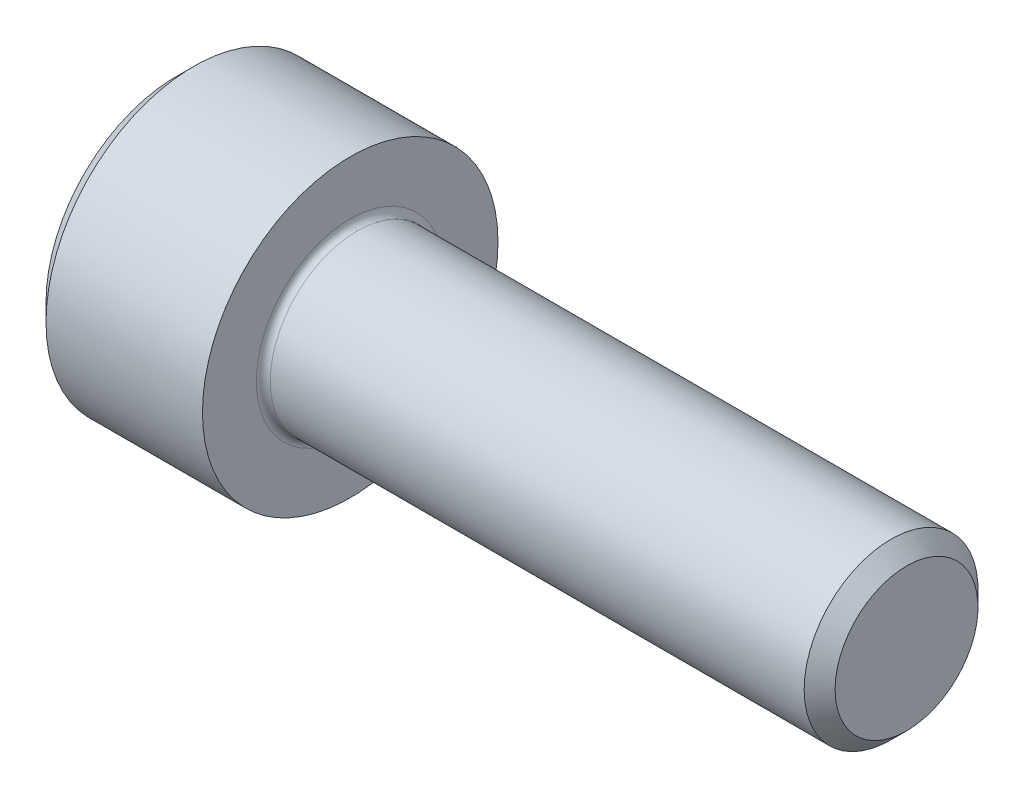
SolidWorks part; units mm, degrees
note: '?' marks a value the reader was unsure of.
revolve "Base-Revolve" add sketch "BodySke"
sketch "BodySke" plane through (0, 0, 0) normal (0, 0, 1) x (1, 0, 0)
  line L0 (0, 0) -> (0, 3.75)
  line L1 (0.5, 4.25) -> (5, 4.25)
  line L2 (5, 4.25) -> (5, 2.5)
  line L3 (5, 2.5) -> (20.555, 2.5)
  line L4 (21, 2.055) -> (21, 0)
  line L5 (21, 0) -> (0, 0)
  line L6 (-31.75, 0) -> (127, 0) construction
  line L7 (0, 3.75) -> (0.5, 4.25)
  line L8 (21, 2.055) -> (20.555, 2.5)
  line L9 (0, -3.75) -> (0.5, -4.25) construction
  line L10 (21, -2.055) -> (20.555, -2.5) construction
  line L11 (5.8, 9.525) -> (5.8, 3.175) construction
  line L12 (13, 9.525) -> (13, 3.175) construction
  line L13 (-29, 9.525) -> (-29, 3.175) construction
  dimension "Diameter" = 5
  dimension "Head_ht" = 5
  dimension "Length" = 16
  dimension "Body_ch_ang" = 45
  dimension "Head_dia" = 8.5
  dimension "Head_ch_ang" = 45
  dimension "Minor_dia" = 4.11
  dimension "Advance" = 0.8
  dimension "Thread_nom" = 8
  dimension "Thread_length" = 50
  dimension "Head_ch_ht" = 0.5
cosmetic thread "ThreadCosmetic" [suppressed]
fillet "Fillet1" radius 0.2 1 edges at (5, 0, 2.5)
ref_plane "Plane1" through (0, 0, 0) normal (0, 0, 1) x (1, 0, 0)
ref_plane "Plane2" through (0, 0, 0) normal (0, 1, 0) x (1, 0, 0)
ref_plane "Plane3" through (0, 0, 0) normal (1, 0, 0) x (0, 0, -1)
sketch "Sketch2" plane through (0, 0, 0) normal (0, 0, 1) x (1, 0, 0)
  line L0 (0, 2.042) -> (2.5, 2.042)
  line L1 (2.5, 2.042) -> (3.6789, 0)
  line L2 (-31.75, 0) -> (127, 0) construction
  line L3 (3.6789, 0) -> (0, 0)
  line L4 (0, 0) -> (0, 2.042)
  line L5 (0, 3.75) -> (0, -3.75) construction
  line L6 (0, 0) -> (47.625, 0) construction
  line L7 (5, -4.25) -> (5, 4.25) construction
  dimension "D2" = 60
revolve "Hex-PreBroach" [suppressed] cut sketch "Sketch2" angle 360 about L6
sketch "Sketch3" plane through (0, 0, 0) normal (-1, 0, 0) x (0, 0.5, 0.866)
  line L0 (1.1789, 2.042) -> (-1.1789, 2.042)
  line L1 (-1.1789, 2.042) -> (-2.3579, 0)
  line L2 (1.1789, 2.042) -> (2.3579, 0)
  line L3 (1.1789, -2.042) -> (2.3579, 0)
  line L4 (1.1789, -2.042) -> (-1.1789, -2.042)
  line L5 (-1.1789, -2.042) -> (-2.3579, 0)
extrude "Hex" [suppressed] cut sketch "Sketch3" against normal blind 2.5
sketch "Sketch4" plane through (0, 0, 0) normal (-1, 0, 0) x (0, 0, 1)
  line L0 (0, 0) -> (2.3876, 0)
  line L1 (0, 0) -> (6.1484, 3.5498) construction
  line L2 (0, 0) -> (1.1938, 2.0677)
  line L3 (1.9883, 0.576) -> (2.2704, 0.7389)
  line L4 (1.493, 1.4339) -> (1.7751, 1.5968)
  arc A0 (1.9883, 0.576) -> (1.493, 1.4339) centre (0, 0) ccw
  arc A1 (2.3876, 0) -> (2.2704, 0.7389) centre (0, 0) ccw
  arc A2 (1.1938, 2.0677) -> (1.7751, 1.5968) centre (0, 0) cw
  dimension "D1" = 30
  dimension "D2" = 60
extrude "Spline" [suppressed] cut sketch "Sketch4" against normal blind 2.5
pattern_circular "CirPattern1" [suppressed] count 0 every? 60?
sketch "Sketch5" plane through (0, 0, 0) normal (0, 0, 1) x (1, 0, 0)
  line L0 (-31.75, 0) -> (127, 0) construction
  line L2 (0, 3.75) -> (0, -3.75) construction
  circle A0 centre (2, 0) radius 0.675
  dimension "Drilled_hole_dia" = 1.35
  dimension "Drilled_hole_loc" = 2
extrude "Hole" [suppressed] cut sketch "Sketch5" against normal through all and the other way through all
pattern_circular "Drilled-4" [suppressed] count 2 every 60
pattern_circular "Drilled-6" [suppressed] count 3 every 60
sketch "ThdSchSke" plane through (0, 0, 0) normal (0, 0, 1) x (1, 0, 0)
  line L0 (5.8, -2.055) -> (5.4884, -2.5)
  line L1 (5.8, -2.055) -> (6.1116, -2.5)
  line L2 (6.1116, -2.5) -> (6.1116, -3.125)
  line L3 (-3.175, 0) -> (5.1513, 0) construction
  line L5 (6.1116, -3.125) -> (5.4884, -3.125)
  line L6 (5.4884, -3.125) -> (5.4884, -2.5)
  line L7 (0, 3.75) -> (0, -3.75) construction
revolve "ThreadSchematic" [suppressed] cut sketch "ThdSchSke" angle 360 about L3
pattern_linear "ThdSchPat" [suppressed]
equation "\"D2@Sketch3\" = \"Hex_size@Sketch3\" / 2"
equation "\"D1@Sketch3\" = \"Hex_size@Sketch3\" / 2"
equation "\"D1@Sketch2\" = \"Hex_size@Sketch3\" / 2"
equation "\"D3@Sketch4\" = \"Spline_p_dim@Sketch4\" / 2"
equation "\"Thread_minor@ThreadCosmetic\"  =  \"Minor_dia@BodySke\""
equation "\"D2@CirPattern1\" = 360 / \"Num_teeth@CirPattern1\""
equation "\"Wall_thickness@Sketch2\" = \"Head_ht@BodySke\" - \"Key_eng@Hex\""
equation "\"Thread_length@ThreadCosmetic\" = ((sgn( (\"Length@BodySke\" - \"Advance@BodySke\" ) - \"Thread_nom@BodySke\" )-1)*( (\"Length@BodySke\" - \"Advance@BodySke\" ) - \"Thread_nom@BodySke\" ))/-2+ \"Thread_nom@BodySke\""
equation "\"Thread_minor@ThdSchSke\" = \"Minor_dia@BodySke\""
equation "\"Diameter@ThdSchSke\" = \"Diameter@BodySke\""
equation "\"Overcut@ThdSchSke\" = \"Diameter@BodySke\" * 1.25"
equation "\"Start@ThdSchSke\" = \"Head_ht@BodySke\" + \"Length@BodySke\" - \"Thread_length@ThreadCosmetic\"  '---Non-countersunk---"
equation "\"Num_threads@ThdSchPat\" = int( \"Thread_length@ThreadCosmetic\" / \"Advance@BodySke\" + 0.999 )  + 1"
equation "\"Advance@ThdSchPat\" = \"Thread_length@ThreadCosmetic\" /  (\"Num_threads@ThdSchPat\" - 1) 'relax it"
equation "\"Num_threads@ThdSchPat\" = \"Num_threads@ThdSchPat\" - sgn( \"Num_threads@ThdSchPat\" - 1) '---chamfered tips only---"
